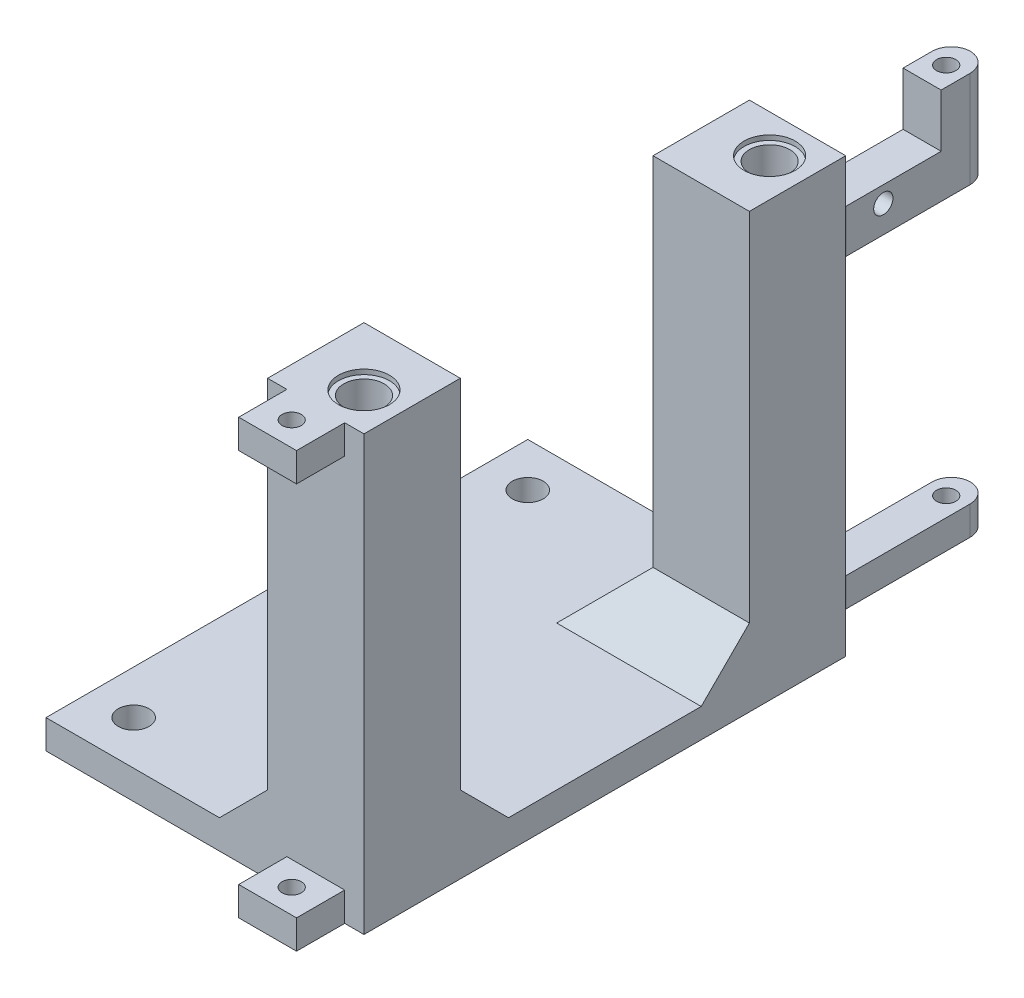
SolidWorks part; units mm, degrees
ref_plane "Front Plane" through (0, 0, 0) normal (0, 0, 1) x (1, 0, 0)
ref_plane "Top Plane" through (0, 0, 0) normal (0, 1, 0) x (1, 0, 0)
ref_plane "Right Plane" through (0, 0, 0) normal (1, 0, 0) x (0, 0, -1)
sketch "Sketch1" plane through (0, 0, 0) normal (0, 1, 0) x (1, 0, 0)
  line L1 (-6.5124, 9.686) -> (1.4876, 9.686)
  line L2 (-6.5124, 9.686) -> (-6.5124, -40.314)
  line L3 (-6.5124, -40.314) -> (1.4876, -40.314)
  line L4 (1.4876, 9.686) -> (1.4876, -40.314)
  line L5 (1.4876, 9.686) -> (26.4876, 9.686)
  line L6 (1.4876, 9.686) -> (1.4876, -40.314)
  line L7 (1.4876, -40.314) -> (26.4876, -40.314)
  line L8 (26.4876, 9.686) -> (26.4876, -40.314)
  circle A0 centre (-1.9624, -35.764) radius 1.6
  circle A1 centre (-1.9624, 5.136) radius 1.6
  dimension "D4" = 3.2
  dimension "D5" = 3.2
  dimension "D6" = 4.55
  dimension "D7" = 4.55
  dimension "D8" = 4.55
  dimension "D9" = 4.55
  dimension "D1" = 8
  dimension "D2" = 50
  dimension "D3" = 25
extrude "Boss-Extrude1" add sketch "Sketch1" along normal blind 3 contours A1 | A0 | L5 L8 L7 L3 L2 L1
sketch "Sketch2" plane through (0, 3, 0) normal (0, 1, 0) x (1, 0, 0)
  line L1 (26.4876, -40.314) -> (16.4876, -40.314)
  line L2 (26.4876, -40.314) -> (26.4876, -30.314)
  line L3 (26.4876, -30.314) -> (16.4876, -30.314)
  line L4 (16.4876, -40.314) -> (16.4876, -30.314)
  line L5 (26.4876, 9.686) -> (16.4876, 9.686)
  line L6 (26.4876, 9.686) -> (26.4876, -0.314)
  line L7 (26.4876, -0.314) -> (16.4876, -0.314)
  line L8 (16.4876, 9.686) -> (16.4876, -0.314)
  dimension "D1" = 10
  dimension "D2" = 10
  dimension "D3" = 10
  dimension "D4" = 10
extrude "Boss-Extrude2" add sketch "Sketch2" along normal blind 42
chamfer "Chamfer1" distance 5 angle 45 4 edges at (16.4876, 3, -4.686) (21.4876, 3, 0.314) (16.4876, 3, 35.314) (21.4876, 3, 30.314)
ref_plane "Plane1" through (0, 45, 0) normal (0, 1, 0) x (1, 0, 0)
sketch "Sketch3" plane through (0, 45, 0) normal (0, 1, 0) x (1, 0, 0)
  line L0 (26.4876, -40.314) -> (26.4876, -30.314) construction
  line L1 (16.4876, -40.314) -> (26.4876, -40.314) construction
  line L2 (26.4876, -0.314) -> (26.4876, 9.686) construction
  line L3 (26.4876, 9.686) -> (16.4876, 9.686) construction
  circle A0 centre (22.5376, -36.364) radius 2.1
  circle A1 centre (22.5376, 5.736) radius 2.1
  dimension "D1" = 4.2
  dimension "D3" = 3.95
  dimension "D4" = 4.2
  dimension "D6" = 3.95
  dimension "D2" = 3.95
  dimension "D5" = 3.95
extrude "Cut-Extrude1" cut sketch "Sketch3" against normal blind 52
sketch "Sketch4" plane through (0, 45, 0) normal (0, 1, 0) x (1, 0, 0)
  circle A0 centre (22.5376, -36.364) radius 2.65
  circle A1 centre (22.5376, 5.736) radius 2.65
  dimension "D1" = 5.3
  dimension "D2" = 5.3
extrude "Cut-Extrude2" cut sketch "Sketch4" against normal blind 0.5
ref_plane "Plane2" through (0, 22.5, 0) normal (0, -1, 0) x (-1, 0, 0)
mirror "Mirror1" about plane through (0, 22.5, 0) normal (0, -1, 0) of "Cut-Extrude2"
sketch "Sketch5" plane through (0, 0, -9.686) normal (0, 0, -1) x (-1, 0, 0)
  line L0 (-22.4876, 36.5) -> (-17.9876, 36.5) construction
  line L1 (-18.2876, 36.2) -> (-22.2399, 36.2)
  line L2 (-18.2876, 36.2) -> (-18.2876, 31.6868)
  line L3 (-18.2876, 31.6868) -> (-22.2399, 31.6868)
  line L4 (-22.2399, 36.2) -> (-22.2399, 31.6868)
  line L5 (-17.9876, 32.25) -> (-17.9876, 37) construction
  dimension "D1" = 0.3
  dimension "D2" = 0.3
extrude "Boss-Extrude3" add sketch "Sketch5" along normal up to surface (14.15 mm away)
sketch "Sketch6" plane through (22.2399, 0, 0) normal (1, 0, 0) x (0, 0, -1)
  circle A0 centre (17.836, 34.5) radius 1
  dimension "D1" = 2
extrude "Cut-Extrude3" cut sketch "Sketch6" against normal up to surface (3.9523 mm away) up to face at (18.2876, 33.9434, -16.761)
sketch "Sketch7" plane through (0, 0, -23.836) normal (0, 0, -1) x (-1, 0, 0)
  line L1 (-22.2399, 31.6868) -> (-18.2876, 31.6868)
  line L2 (-22.2399, 31.6868) -> (-22.2399, 41.7057)
  line L3 (-22.2399, 41.7057) -> (-18.2876, 41.7057)
  line L4 (-18.2876, 31.6868) -> (-18.2876, 41.7057)
  point P5 (-18.2876, 31.6868)
extrude "Boss-Extrude4" add sketch "Sketch7" along normal blind 5
sketch "Sketch8" plane through (0, 0, -9.686) normal (0, 0, -1) x (-1, 0, 0)
  line L0 (-18.2876, 41.7057) -> (-22.2399, 41.7057) construction
  line L1 (-22.2399, 36.2) -> (-18.2687, 36.2)
  line L2 (-22.2399, 36.2) -> (-22.2399, 41.7057)
  line L3 (-22.2399, 41.7057) -> (-18.2687, 41.7057)
  line L4 (-18.2687, 36.2) -> (-18.2687, 41.7057)
  point P5 (-18.2687, 36.2)
extrude "Boss-Extrude5" add sketch "Sketch8" along normal up to surface (2.15 mm away)
sketch "Sketch9" plane through (0, 0, -9.686) normal (0, 0, -1) x (-1, 0, 0)
  line L0 (6.5124, 0) -> (-26.4876, 0) construction
  line L1 (-22.2399, 0) -> (-18.2876, 0)
  line L2 (-22.2399, 0) -> (-22.2399, 3)
  line L3 (-22.2399, 3) -> (-18.2876, 3)
  line L4 (-18.2876, 0) -> (-18.2876, 3)
  line L5 (6.5124, 3) -> (-11.4876, 3) construction
  line L6 (-22.2399, 41.7057) -> (-22.2399, 31.6868) construction
  line L7 (-18.2876, 31.6868) -> (-18.2876, 41.7057) construction
extrude "Boss-Extrude6" add sketch "Sketch9" along normal up to surface (19.15 mm away) up to face at (20.2638, 36.6962, -28.836)
sketch "Sketch10" plane through (0, 41.7057, 0) normal (0, 1, 0) x (1, 0, 0)
  line L0 (18.2876, 23.836) -> (22.2399, 28.836) construction
  line L1 (18.2876, 28.836) -> (22.2399, 23.836) construction
  circle A0 centre (20.2638, 26.336) radius 1
  dimension "D1" = 2
extrude "Cut-Extrude4" cut sketch "Sketch10" against normal through all
fillet "Fillet3" radius 2 4 edges at (18.2876, 1.5, -28.836) (22.2399, 1.5, -28.836) (18.2876, 36.6962, -28.836) (22.2399, 36.6962, -28.836)
fillet "Fillet4" radius 4.25 1 edges at (22.2399, 1.5, -9.686)
fillet "Fillet5" radius 4.25 1 edges at (18.2876, 1.5, -9.686)
fillet "Fillet6" radius 4.25 1 edges at (22.2399, 36.6962, -9.686)
fillet "Fillet7" radius 4.25 1 edges at (18.2876, 33.9434, -9.686)
fillet "Fillet8" radius 1 1 edges at (20.2626, 3, -9.686)
fillet "Fillet9" radius 1 1 edges at (21.4876, 31.6868, -9.686)
sketch "Sketch11" plane through (0, 0, 40.314) normal (0, 0, 1) x (1, 0, 0)
  line L0 (16.4876, 45) -> (26.4876, 45) construction
  line L1 (18.4876, 45) -> (24.4876, 45)
  line L2 (18.4876, 45) -> (18.4876, 42)
  line L3 (18.4876, 42) -> (24.4876, 42)
  line L4 (24.4876, 45) -> (24.4876, 42)
  line L5 (-6.5124, 0) -> (26.4876, 0) construction
  line L6 (18.4876, 0) -> (24.4876, 0)
  line L7 (18.4876, 0) -> (18.4876, 3)
  line L8 (18.4876, 3) -> (24.4876, 3)
  line L9 (24.4876, 0) -> (24.4876, 3)
  line L10 (21.4876, 8) -> (21.4876, 0) construction
  line L11 (21.4876, 8) -> (21.4876, 45) construction
  line L13 (-6.5124, 3) -> (11.4876, 3) construction
  line L14 (16.4876, 8) -> (26.4876, 8) construction
  line L15 (26.4876, 8) -> (39.3241, 4.4212) construction
  line L16 (39.3241, 4.4212) -> (39.5028, 4.4212) construction
  dimension "D1" = 3
  dimension "D2" = 3
  dimension "D3" = 3
  dimension "D4" = 3
  dimension "D5" = 3
extrude "Boss-Extrude7" add sketch "Sketch11" along normal blind 5
sketch "Sketch12" plane through (0, 0, 0) normal (0, -1, 0) x (1, 0, 0)
  line L0 (18.4876, 45.314) -> (24.4876, 40.314) construction
  line L1 (18.4876, 40.314) -> (24.4876, 45.314) construction
  circle A0 centre (21.4876, 42.814) radius 1
  dimension "D1" = 2
extrude "Cut-Extrude5" cut sketch "Sketch12" against normal through all
